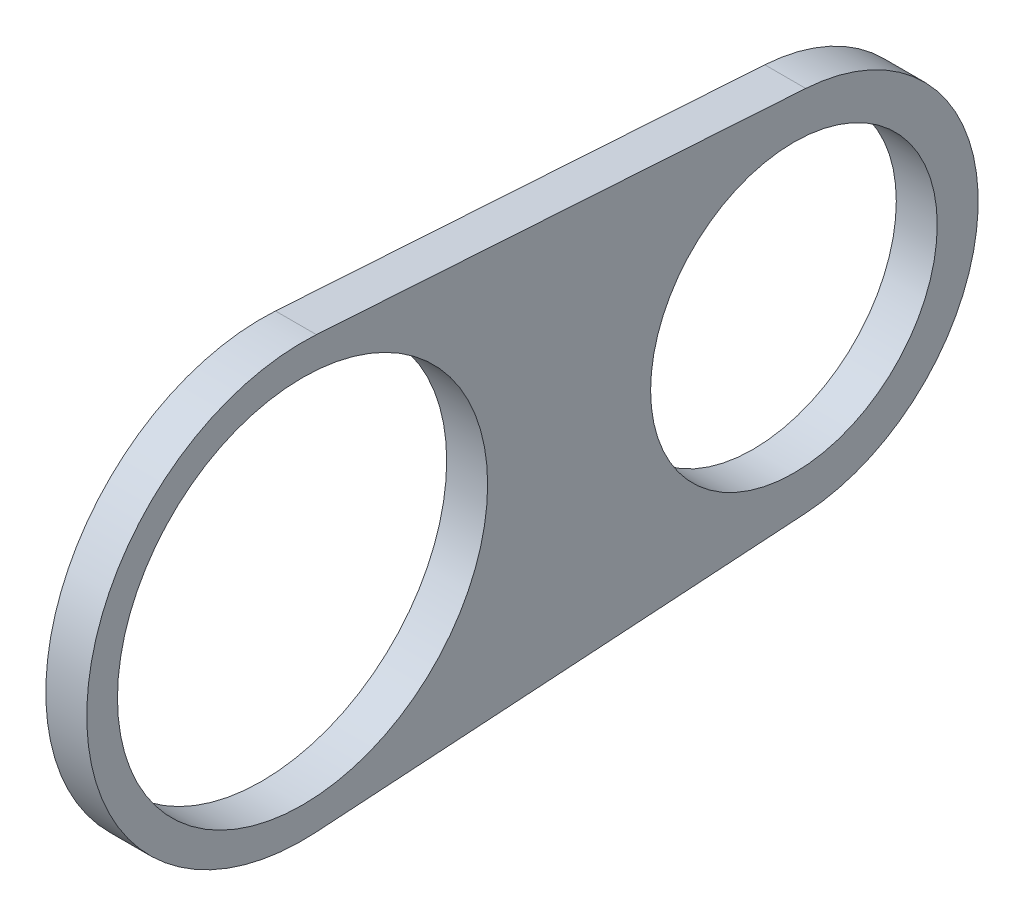
SolidWorks part; units mm, degrees
material "6061-T6 (SS)"
ref_plane "Front" through (0, 0, 0) normal (0, 0, 1) x (1, 0, 0)
ref_plane "Top" through (0, 0, 0) normal (0, 1, 0) x (1, 0, 0)
ref_plane "Right" through (0, 0, 0) normal (1, 0, 0) x (0, 0, -1)
sketch "Sketch1" plane through (0, 0, 0) normal (1, 0, 0) x (0, 0, -1)
  line L0 (-17.9763, 16.6978) -> (19.9668, 14.2581)
  line L3 (-17.9763, -16.6978) -> (19.9668, -14.2581)
  line L4 (-19.05, 0) -> (19.05, 0) construction
  circle A2 centre (-19.05, 0) radius 14.351
  circle A3 centre (19.05, 0) radius 11.1125
  arc A4 (19.9668, -14.2581) -> (19.9668, 14.2581) centre (19.05, 0) ccw
  arc A5 (-17.9763, 16.6978) -> (-17.9763, -16.6978) centre (-19.05, 0) ccw
  point P13 (0, 0)
  dimension "D1" = 28.702
  dimension "D2" = 2.3812
  dimension "D4" = 22.225
  dimension "D3" = 3.175
  dimension "D5" = 38.1
extrude "Boss-Extrude1" add sketch "Sketch1" along normal blind 3.175
